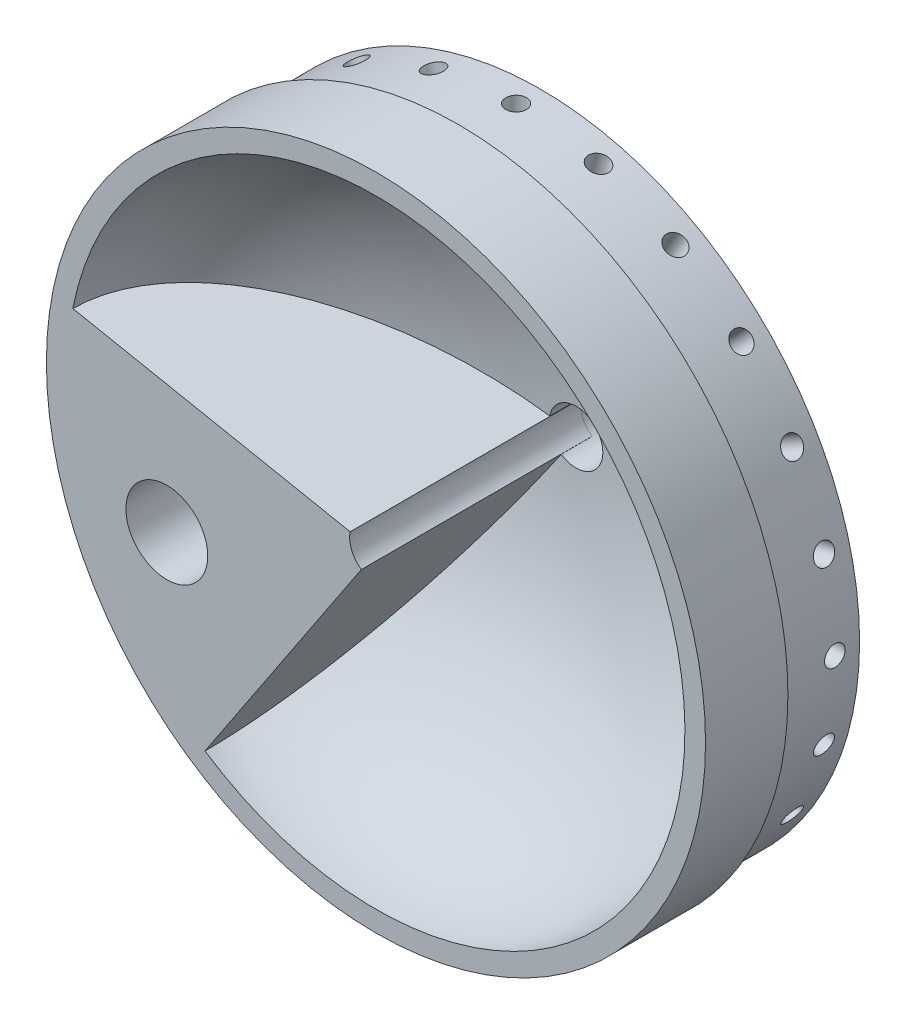
SolidWorks part; units mm, degrees
material "6061-T4 (SS)"
ref_plane "Front Plane" through (0, 0, 0) normal (0, 0, 1) x (1, 0, 0)
ref_plane "Top Plane" through (0, 0, 0) normal (0, 1, 0) x (1, 0, 0)
ref_plane "Right Plane" through (0, 0, 0) normal (1, 0, 0) x (0, 0, -1)
ref_plane "Plane1" through (0, 0, -65.0875) normal (0, 0, 1) x (1, 0, 0)
sketch "Sketch1" plane through (0, 0, 0) normal (0, 1, 0) x (1, 0, 0)
  line L1 (95.25, 0) -> (101.6, 0)
  line L2 (0, 0) -> (0, 61.9125) construction
  line L4 (101.6, 50.8) -> (101.6, 0)
  line L8 (0, 75.8825) -> (17.78, 75.8825)
  line L10 (8.255, 0) -> (8.255, 75.8825)
  line L11 (8.255, 75.8825) -> (-8.255, 75.8825)
  line L12 (-8.255, 75.8825) -> (-8.255, 0)
  line L13 (-8.255, 0) -> (8.255, 0)
  line L14 (8.255, 61.9125) -> (0, 61.9125) construction
  line L15 (17.78, 75.8825) -> (68.9944, 50.8)
  line L16 (68.9944, 50.8) -> (93.98, 50.8)
  line L17 (60.1117, 55.1503) -> (57.3188, 49.4475) construction
  line L18 (93.98, 50.8) -> (101.6, 50.8)
  line L19 (57.3188, 49.4475) -> (16.9049, 69.2404) construction
  ellipse E0 centre (0, 0) end of major axis (-95.25, 0) minor radius 61.9125
  point P18 (17.78, 75.8825)
  dimension "D1" = 6.35
  dimension "D2" = 101.6
  dimension "D3" = 61.9125
  dimension "D4" = 50.8
  dimension "D5" = 13.97
  dimension "D6" = 16.51
  dimension "D7" = 6.35
  dimension "D10" = 17.78
revolve "Revolve1" add sketch "Sketch1" angle 360 about L2 region at (67.1309, 0, -45.0449) other way angle 360
sketch "Sketch3" plane through (0, 0, 0) normal (0, 0, -1) x (-1, 0, 0)
  circle A0 centre (0, 0) radius 101.6
  circle A1 centre (0, 0) radius 98.298
  dimension "D1" = 203.2
  dimension "D2" = 3.302
extrude "Cut-Extrude2" cut sketch "Sketch3" along normal through all from offset 25.4
ref_plane "Plane2" through (0, -98.298, 0) normal (0, -1, 0) x (-1, 0, 0)
sketch "Sketch11" plane through (0, -98.298, 0) normal (0, -1, 0) x (-1, 0, 0)
  line L0 (0, 0) -> (0, 50.8) construction
  line L2 (98.298, 50.8) -> (-98.298, 50.8) construction
  circle A0 centre (0, 43.18) radius 3.175
  dimension "D2" = 6.35
  dimension "D1" = 43.18
extrude "Cut-Extrude3" cut sketch "Sketch11" against normal blind 12.7
pattern_circular "CirPattern1" count 24 over 360 about axis through (0, 0, 0) along (0, 0, 1) of "Cut-Extrude3"
sketch "Sketch13" plane through (0, 0, 0) normal (0, 1, 0) x (1, 0, 0)
  line L0 (98.298, 50.8) -> (-98.298, 50.8) construction
  line L1 (68.9944, 50.8) -> (17.78, 75.8825) construction
  line L2 (98.298, 50.8) -> (-98.298, 50.8) construction
  line L3 (68.9944, 50.8) -> (43.0631, 63.5)
  line L4 (43.0631, 63.5) -> (98.298, 63.5)
  line L5 (98.298, 63.5) -> (98.298, 50.8)
  line L6 (68.9944, 50.8) -> (98.298, 50.8)
  dimension "D1" = 12.7
ref_axis "Axis1" through (0, 0, -79.6766) along (0, 0, 1)
ref_plane "Plane3" through (0, 0, -53.34) normal (0, 0, -1) x (-1, 0, 0)
sketch "Sketch21" plane through (0, 0, 0) normal (0, 0, 1) x (1, 0, 0)
  line L0 (0, 0) -> (-93.4496, 18.432)
  line L1 (0, 0) -> (-52.7155, -79.3324)
  line L2 (-56.9623, 11.2353) -> (-64.4772, -26.8647) construction
  line L3 (-64.4772, -26.8647) -> (-32.1328, -48.3572) construction
  line L4 (-64.4772, -26.8647) -> (-87.9234, -36.6337) construction
  circle A0 centre (0, 0) radius 98.298 construction
  circle A1 centre (0, 0) radius 98.298
  circle A2 centre (0, 0) radius 95.25 construction
  arc A3 (-93.4496, 18.432) -> (-52.7155, -79.3324) centre (0, 0) ccw
  circle A4 centre (-64.4772, -26.8647) radius 12.5916
  dimension "D1" = 25.4
  dimension "D2" = 38.1
extrude "Boss-Extrude2" add sketch "Sketch21" against normal blind 71.12 contours L1 A3 L0 | A4
sketch "Sketch33" plane through (0, 0, -53.34) normal (0, 0, -1) x (-1, 0, 0)
  circle A0 centre (0, 0) radius 8.1171
extrude "Cut-Extrude5" cut sketch "Sketch33" against normal blind 201.168 and the other way blind 251.46
sketch "Sketch34" plane through (0, 0, -53.34) normal (0, 0, -1) x (-1, 0, 0)
  circle A0 centre (64.4772, -26.8647) radius 12.6121
extrude "Cut-Extrude6" cut sketch "Sketch34" against normal blind 201.168 and the other way blind 301.752
equation "\"12.5.00deg\"=25"
